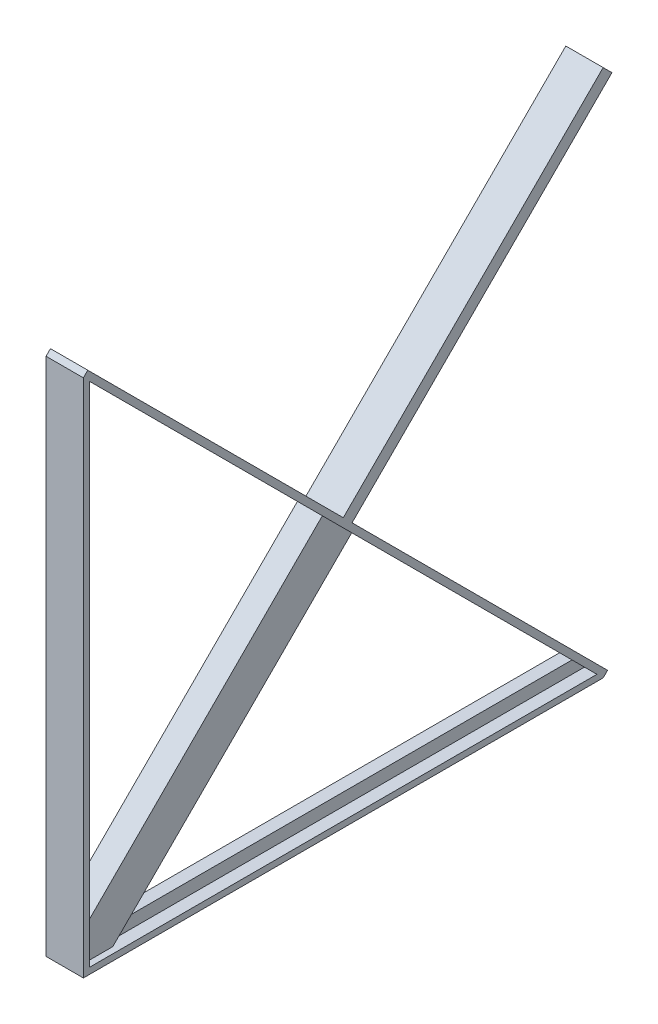
SolidWorks part; units mm, degrees
ref_plane "前视基准面" through (0, 0, 0) normal (0, 0, 1) x (1, 0, 0)
ref_plane "上视基准面" through (0, 0, 0) normal (0, 1, 0) x (1, 0, 0)
ref_plane "右视基准面" through (0, 0, 0) normal (1, 0, 0) x (0, 0, -1)
sketch "草图1" plane through (0, 0, 0) normal (1, 0, 0) x (0, 0, -1)
  line L0 (0, 0) -> (0, 2121.32)
  line L1 (0, 0) -> (2121.32, 0)
  line L3 (25.4, 2095.92) -> (25.4, 25.4)
  line L4 (25.4, 25.4) -> (2095.92, 25.4)
  line L6 (2121.32, 0) -> (2095.92, 25.4)
  line L7 (0, 2121.32) -> (25.4, 2095.92)
  point P3 (25.4, 2095.92)
  point P8 (2095.92, 25.4)
  dimension "D1" = 2121.32
  dimension "D2" = 2121.32
  dimension "D3" = 25.4
  dimension "D4" = 25.4
  dimension "D5" = 25.4
  dimension "D6" = 25.4
extrude "凸台-拉伸2" add sketch "草图1" along normal blind 76.2 and the other way blind 76.2
sketch "草图3" plane through (0, 0, 0) normal (1, 0, 0) x (0, 0, -1)
  line L0 (25.4, 2095.92) -> (25.4, 25.4)
  line L1 (25.4, 25.4) -> (2095.92, 25.4)
  line L2 (2095.92, 25.4) -> (25.4, 25.4) construction
  line L4 (76.2, 2045.12) -> (76.2, 76.2)
  line L5 (76.2, 76.2) -> (2045.12, 76.2)
  line L7 (76.2, 2045.12) -> (25.4, 2095.92)
  line L8 (2045.12, 76.2) -> (2095.92, 25.4)
  point P4 (2045.12, 76.2)
  point P8 (76.2, 1192.1642)
  point P11 (76.2, 2045.12)
  dimension "D1" = 50.8
  dimension "D2" = 50.8
  dimension "D3" = 2070.52
  dimension "D4" = 50.8
  dimension "D5" = 50.8
extrude "凸台-拉伸3" add sketch "草图3" along normal blind 25.4 and the other way blind 25.4
sketch "草图4" plane through (0, 1060.66, -1060.66) normal (0, 0.7071, -0.7071) x (1, 0, 0)
  line L1 (-76.2, -1499.9998) -> (76.2, -1499.9998)
  line L2 (-76.2, -1499.9998) -> (-76.2, 1499.9998)
  line L3 (-76.2, 1499.9998) -> (76.2, 1499.9998)
  line L4 (76.2, -1499.9998) -> (76.2, 1499.9998)
extrude "凸台-拉伸4" add sketch "草图4" along normal blind 25.4
sketch "草图5" plane through (25.4, 0, 0) normal (1, 0, 0) x (0, 0, -1)
  line L0 (25.4, 25.4) -> (25.4, 145.4)
  line L1 (25.4, 25.4) -> (25.4, 2095.92) construction
  line L2 (25.4, 145.4) -> (1000.66, 1120.66)
  line L3 (25.4, 2095.92) -> (2095.92, 25.4) construction
  line L4 (1000.66, 1120.66) -> (1120.66, 1000.66)
  line L5 (1120.66, 1000.66) -> (145.4, 25.4)
  line L6 (25.4, 25.4) -> (2095.92, 25.4) construction
  line L7 (145.4, 25.4) -> (25.4, 25.4)
  dimension "D1" = 120
  dimension "D2" = 120
extrude "凸台-拉伸5" add sketch "草图5" along normal blind 25.4 and the other way blind 76.2
sketch "草图6" plane through (0, 1078.6205, -1078.6205) normal (0, 0.7071, -0.7071) x (1, 0, 0)
  line L0 (-76.2, 0) -> (76.2, 0) construction
  line L1 (-76.2, 1499.9998) -> (-76.2, -1499.9998) construction
  line L2 (76.2, -1499.9998) -> (76.2, 1499.9998) construction
  line L5 (76.2, 25.4) -> (-76.2, 25.4)
  line L6 (76.2, 25.4) -> (76.2, -25.4)
  line L7 (76.2, -25.4) -> (-76.2, -25.4)
  line L8 (-76.2, 25.4) -> (-76.2, -25.4)
  line L9 (76.2, 25.4) -> (-76.2, -25.4) construction
  line L10 (76.2, -25.4) -> (-76.2, 25.4) construction
  point P6 (0, 0)
  dimension "D1" = 50.8
extrude "凸台-拉伸6" add sketch "草图6" along normal blind 1500
